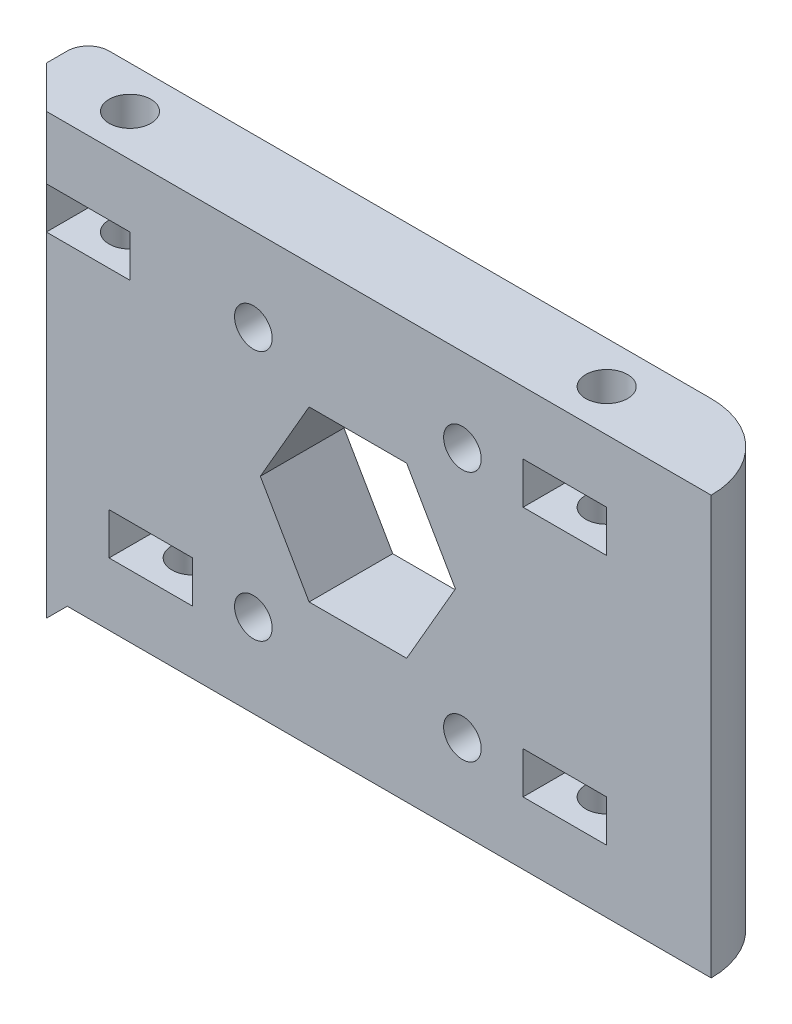
SolidWorks part; units mm, degrees
ref_plane "Front Plane" through (0, 0, 0) normal (0, 0, 1) x (1, 0, 0)
ref_plane "Top Plane" through (0, 0, 0) normal (0, 1, 0) x (1, 0, 0)
ref_plane "Right Plane" through (0, 0, 0) normal (1, 0, 0) x (0, 0, -1)
sketch "Sketch1" plane through (0, 0, 0) normal (0, 0, 1) x (1, 0, 0)
  line L0 (-9.3359, -18.2969) -> (-6.3359, -15.2969)
  line L1 (-9.3359, 4.7031) -> (24.4641, 4.7031)
  line L2 (-9.3359, 4.7031) -> (-9.3359, -15.2969)
  line L3 (-9.3359, -15.2969) -> (24.4641, -15.2969)
  line L4 (24.4641, 4.7031) -> (24.4641, -15.2969)
  line L5 (12.2298, -5.2969) -> (9.8969, -1.2564)
  line L6 (9.8969, -1.2564) -> (5.2313, -1.2564)
  line L7 (5.2313, -1.2564) -> (2.8984, -5.2969)
  line L8 (2.8984, -5.2969) -> (5.2313, -9.3375)
  line L9 (5.2313, -9.3375) -> (9.8969, -9.3375)
  line L10 (9.8969, -9.3375) -> (12.2298, -5.2969)
  line L35 (-9.3359, -15.2969) -> (-6.3359, -15.2969)
  line L36 (-9.3359, -15.2969) -> (-9.3359, -18.2969)
  line L37 (-9.3359, -18.2969) -> (-6.3359, -18.2969)
  line L38 (-6.3359, -15.2969) -> (-6.3359, -18.2969)
  line L40 (-4.3359, -10.2969) -> (-0.3359, -10.2969)
  line L41 (-4.3359, -10.2969) -> (-4.3359, -12.2969)
  line L42 (-4.3359, -12.2969) -> (-0.3359, -12.2969)
  line L43 (-0.3359, -10.2969) -> (-0.3359, -12.2969)
  line L44 (15.4641, -10.2969) -> (19.4641, -10.2969)
  line L45 (15.4641, -10.2969) -> (15.4641, -12.2969)
  line L46 (15.4641, -12.2969) -> (19.4641, -12.2969)
  line L47 (19.4641, -10.2969) -> (19.4641, -12.2969)
  line L48 (15.4641, 1.7031) -> (19.4641, 1.7031)
  line L49 (15.4641, 1.7031) -> (15.4641, -0.2969)
  line L50 (15.4641, -0.2969) -> (19.4641, -0.2969)
  line L51 (19.4641, 1.7031) -> (19.4641, -0.2969)
  line L52 (-7.3359, 1.7031) -> (-3.3359, 1.7031)
  line L53 (-7.3359, 1.7031) -> (-7.3359, -0.2969)
  line L54 (-7.3359, -0.2969) -> (-3.3359, -0.2969)
  line L55 (-3.3359, 1.7031) -> (-3.3359, -0.2969)
  circle A0 centre (7.5641, -5.2969) radius 4.0406 construction
  circle A1 centre (2.5641, -11.2969) radius 0.9
  circle A2 centre (12.5641, -11.2969) radius 0.9
  circle A3 centre (2.5641, 0.7031) radius 0.9
  circle A4 centre (12.5641, 0.7031) radius 0.9
  point P17 (17.4641, -12.2969)
  point P25 (-5.3359, 1.7031)
  point P26 (17.4641, 1.7031)
  point P51 (-2.3359, -12.2969)
  dimension "D23" = 5
  dimension "D24" = 5
  dimension "D1" = 33.8
  dimension "D2" = 20
  dimension "D3" = 10
  dimension "D4" = 16.9
  dimension "D5" = 4
  dimension "D6" = 2
  dimension "D7" = 3
  dimension "D8" = 7
  dimension "D9" = 3
  dimension "D10" = 4
  dimension "D11" = 2
  dimension "D12" = 4
  dimension "D13" = 2
  dimension "D14" = 4
  dimension "D15" = 7
  dimension "D16" = 3
  dimension "D17" = 3
  dimension "D18" = 3
  dimension "D19" = 7
  dimension "D20" = 2
  dimension "D21" = 4
  dimension "D22" = 3
  dimension "D25" = 5
  dimension "D26" = 5
  dimension "D27" = 4
  dimension "D28" = 4
  dimension "D29" = 4
  dimension "D30" = 4
extrude "Boss-Extrude1" add sketch "Sketch1" along normal blind 4 contours L4 L1 L2 L3 L46 L50 L10 L9 L8 L7 L6 L5 | L3 L36 L0 region at (-8.3359, -16.2969, 0) region at (-7.8359, -14.9042, 0)
sketch "Sketch3" plane through (0, -15.2969, 0) normal (0, -1, 0) x (1, 0, 0)
  line L1 (24.4641, 0) -> (-9.3359, 0)
  line L3 (24.4641, 4) -> (-9.3359, 4)
  line L4 (-9.3359, 0) -> (-9.3359, 4)
  circle A0 centre (17.4641, 2) radius 1
  circle A1 centre (-2.3359, 2) radius 1
  dimension "D2" = 7
  dimension "D3" = 2
  dimension "D4" = 2
extrude "Cut-Extrude1" cut sketch "Sketch3" against normal blind 20 contours A0 region at (17.4641, -15.2969, 2)
extrude "Cut-Extrude2" cut sketch "Sketch3<3>" against normal blind 10 contours A1 region at (-2.3359, -15.2969, 2)
sketch "Sketch3<3>" plane through (0, -15.2969, 0) normal (0, -1, 0) x (1, 0, 0) same geometry as "Sketch3"
sketch "Sketch5" plane through (0, 4.7031, 0) normal (0, 1, 0) x (1, 0, 0)
  line L0 (-9.3359, 0) -> (-9.3359, -4)
  circle A0 centre (-5.3359, -2) radius 1
  dimension "D2" = 2
  dimension "D1" = 4
extrude "Cut-Extrude3" cut sketch "Sketch5" against normal blind 10 contours A0 region at (-5.3359, 4.7031, 2)
chamfer "Chamfer2" distance 2 angle 45 1 edges at (-9.3359, -6.7969, 0)
fillet "Fillet2" radius 1 1 edges at (-9.3359, -6.7969, 4)
fillet "Fillet3" radius 4 1 edges at (24.4641, -5.2969, 4)
mirror "Mirror1" about plane through (0, 0, 0) normal (0, 0, 1) of bodies 104
sketch "Sketch6" plane through (0, 4.7031, 0) normal (0, 1, 0) x (1, 0, 0)
  line L1 (24.4641, 0) -> (-10.9963, 0)
  line L2 (24.4641, 0) -> (24.4641, -4.3195)
  line L3 (24.4641, -4.3195) -> (-10.9963, -4.3195)
  line L4 (-10.9963, 0) -> (-10.9963, -4.3195)
extrude "Cut-Extrude4" cut sketch "Sketch6" against normal blind 29
